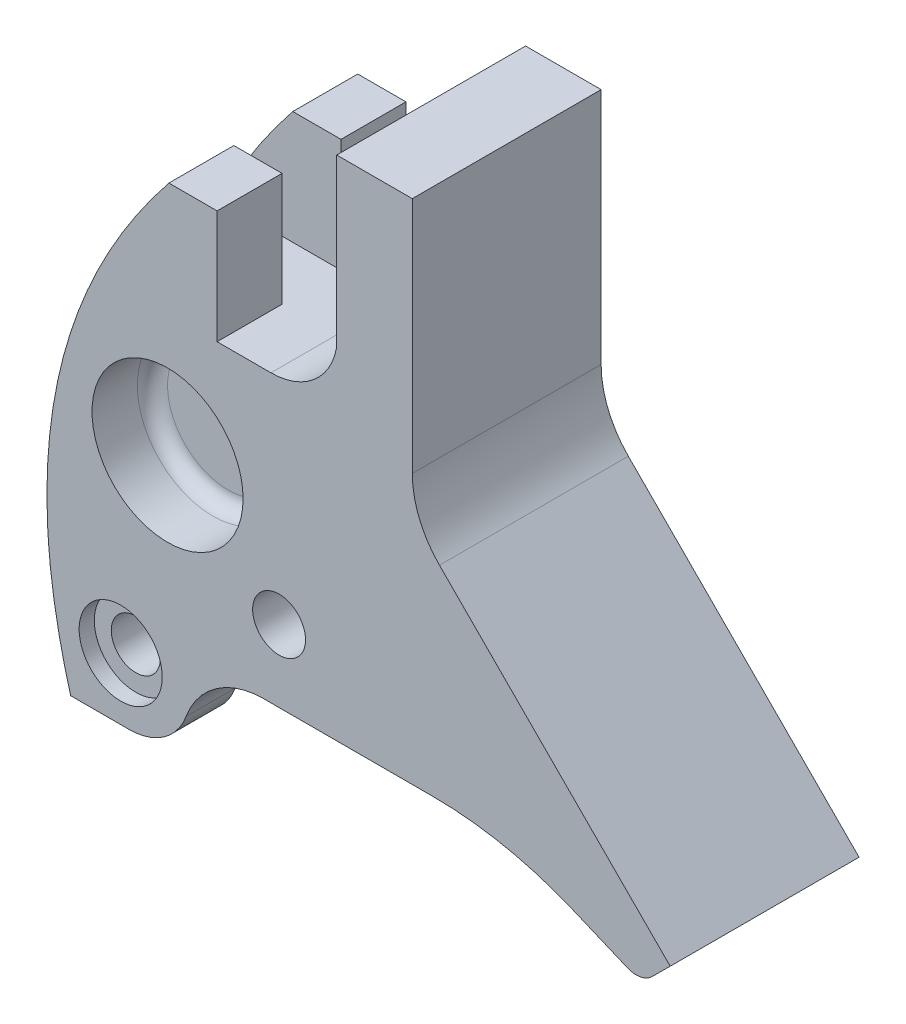
SolidWorks part; units mm, degrees
ref_plane "Front Plane" through (0, 0, 0) normal (0, 0, 1) x (1, 0, 0)
ref_plane "Top Plane" through (0, 0, 0) normal (0, 1, 0) x (1, 0, 0)
ref_plane "Right Plane" through (0, 0, 0) normal (1, 0, 0) x (0, 0, -1)
sketch "Sketch1" plane through (0, 0, 0) normal (0, 0, 1) x (1, 0, 0)
  line L6 (-3.3687, 19.2729) -> (27.1776, -11.4296)
  line L9 (-4.3508, -7.665) -> (-26.6408, -7.665)
  line L11 (-44.4429, -20.0984) -> (-52.1853, -20.0984)
  line L14 (-32.8036, 30.1777) -> (-25.6724, 30.1777)
  line L16 (-39.1853, 45.1777) -> (-32.8036, 45.1777)
  line L17 (-32.8036, 45.1777) -> (-32.8036, 30.1777)
  line L27 (-16.9671, 59.4978) -> (-16.9671, 37.4978)
  line L28 (-16.9671, 59.4978) -> (-6.9671, 59.4978)
  line L29 (-6.9671, 59.4978) -> (-6.9671, 27.9917)
  line L31 (27.1776, -11.4296) -> (24.7954, -13.7997)
  line L32 (21.5175, -14.4388) -> (14.3793, -11.4398)
  arc A7 (-25.6724, 30.1777) -> (-16.9671, 37.4978) centre (-25.6724, 39.0141) ccw
  circle A8 centre (-45.565, -11.8998) radius 3.25
  arc A9 (14.3793, -11.4398) -> (-4.3508, -7.665) centre (-4.3508, -56.0215) ccw
  circle A10 centre (-24.5991, 1.8512) radius 3.5
  arc A11 (-36.9064, -14.8348) -> (-44.4429, -20.0984) centre (-44.4429, -12.0712) cw
  arc A12 (-6.9671, 27.9917) -> (-3.3687, 19.2729) centre (5.3946, 27.9917) ccw
  arc A13 (-26.6408, -7.665) -> (-36.9064, -14.8348) centre (-26.6408, -18.599) ccw
  circle A15 centre (-45.565, -11.8998) radius 5.5 construction
  arc A16 (24.7954, -13.7997) -> (21.5175, -14.4388) centre (22.6795, -11.6729) cw
  spline S0 degree 2 poles (-39.1853, 45.1777) (-62.4565, 16.1628) (-52.1853, -20.0984) knots 0 0 0 1 1 1
  point P17 (4.6851, -38.0674)
  point P39 (-63.0295, 16.1663)
  dimension "D4" = 10.934
  dimension "D7" = 48.3565
  dimension "D2" = 22
  dimension "D3" = 8.8363
  dimension "D9" = 6.5
  dimension "D11" = 7
  dimension "D5" = 8.0272
  dimension "D12" = 12.3617
  dimension "D8" = 11
  dimension "D13" = 3
  dimension "D1" = 15
  dimension "D6" = 90
  dimension "D10" = 10
extrude "Boss-Extrude1" add sketch "Sketch1" along normal blind 25
sketch "Sketch3" plane through (-32.8036, 0, 0) normal (1, 0, 0) x (0, 0, -1)
  line L0 (-25, 45.1777) -> (0, 45.1777) construction
  line L1 (-16.4, 45.1777) -> (-8.6, 45.1777)
  line L2 (-16.4, 45.1777) -> (-16.4, 30.1777)
  line L3 (-16.4, 30.1777) -> (-8.6, 30.1777)
  line L4 (-8.6, 45.1777) -> (-8.6, 30.1777)
  line L5 (-25, 30.1777) -> (0, 30.1777) construction
  line L7 (0, 30.1777) -> (0, 45.1777) construction
  line L8 (-25, 30.1777) -> (-25, 45.1777) construction
  dimension "D1" = 7.8
  dimension "D2" = 8.6
  dimension "D3" = 8.6
extrude "Cut-Extrude3" cut sketch "Sketch3" against normal blind 15
sketch "Sketch5" plane through (0, 0, 25) normal (0, 0, 1) x (1, 0, 0)
  line L2 (-52.1853, -20.0984) -> (-44.4429, -20.0984) construction
  line L3 (-48.3141, -20.0984) -> (-44.4429, -20.0984) construction
  line L8 (-52.1853, -20.0984) -> (-44.4429, -20.0984)
  arc A0 (-36.9064, -14.8348) -> (-44.4429, -20.0984) centre (-44.4429, -12.0712) cw
  arc A1 (-26.6408, -7.665) -> (-36.9064, -14.8348) centre (-26.6408, -18.599) ccw construction
  arc A2 (-26.6408, -7.665) -> (-36.9064, -14.8348) centre (-26.6408, -18.599) ccw
  parabola Q0 (-39.1853, 45.1777) -> (-52.1853, -20.0984) focus (-22.3215, 8.5606) apex (-53.8587, 15.3737) construction
  parabola Q1 (-39.1853, 45.1777) -> (-52.1853, -20.0984) focus (-22.3215, 8.5606) apex (-53.8587, 15.3737) construction
  spline S0 degree 2 poles (-54.9001, -6.4938) (-54.1607, -13.1675) (-52.1853, -20.0984) knots 0.808188 0.808188 0.808188 1 1 1
  spline S2 degree 3 poles (-26.6408, -7.665) (-35.9137, -5.7973) (-45.3331, -5.387) (-54.7746, -6.4791) (-54.9001, -6.4938) knots 0 0 0 0 1 1.01347 1.01347 1.01347 1.01347
  point P3 (-53.8587, 15.3737)
  point P10 (-26.6408, -7.665)
  point P13 (-32.9015, -9.6349)
  point P14 (-39.1853, 45.1777)
  point P15 (-45.565, -5.8998)
  point P17 (-36.9064, -14.8348)
extrude "Cut-Extrude4" cut sketch "Sketch5" against normal blind 18.5
extrude "Boss-Extrude2" add sketch "Sketch5<2>" against normal blind 6.5
sketch "Sketch5<2>" plane through (0, 0, 25) normal (0, 0, 1) x (1, 0, 0) same geometry as "Sketch5"
sketch "Sketch7" plane through (0, 0, 0) normal (0, 0, -1) x (-1, 0, 0)
  circle A0 centre (45.565, -11.8998) radius 3.25
  dimension "D1" = 6.5
extrude "Cut-Extrude5" cut sketch "Sketch7" against normal through all
sketch "Sketch8" plane through (0, 0, 25) normal (0, 0, 1) x (1, 0, 0)
  circle A0 centre (-45.565, -11.8998) radius 5.5
  dimension "D1" = 11
extrude "Cut-Extrude6" cut sketch "Sketch8" against normal blind 2
sketch "Sketch10" plane through (0, 0, 25) normal (0, 0, 1) x (1, 0, 0)
  circle A0 centre (-39.3625, 13.8976) radius 10
sketch "Sketch11" plane through (0, 0, 0) normal (0, 0, -1) x (-1, 0, 0)
  circle A0 centre (39.3625, 13.8976) radius 10
extrude "Cut-Extrude7" cut sketch "Sketch10" against normal blind 8
extrude "Cut-Extrude8" cut sketch "Sketch11" against normal blind 8
fillet "Fillet1" radius 2 1 edges at (-49.3625, 13.8976, 8)
fillet "Fillet2" radius 2 1 edges at (-29.3625, 13.8976, 17)
